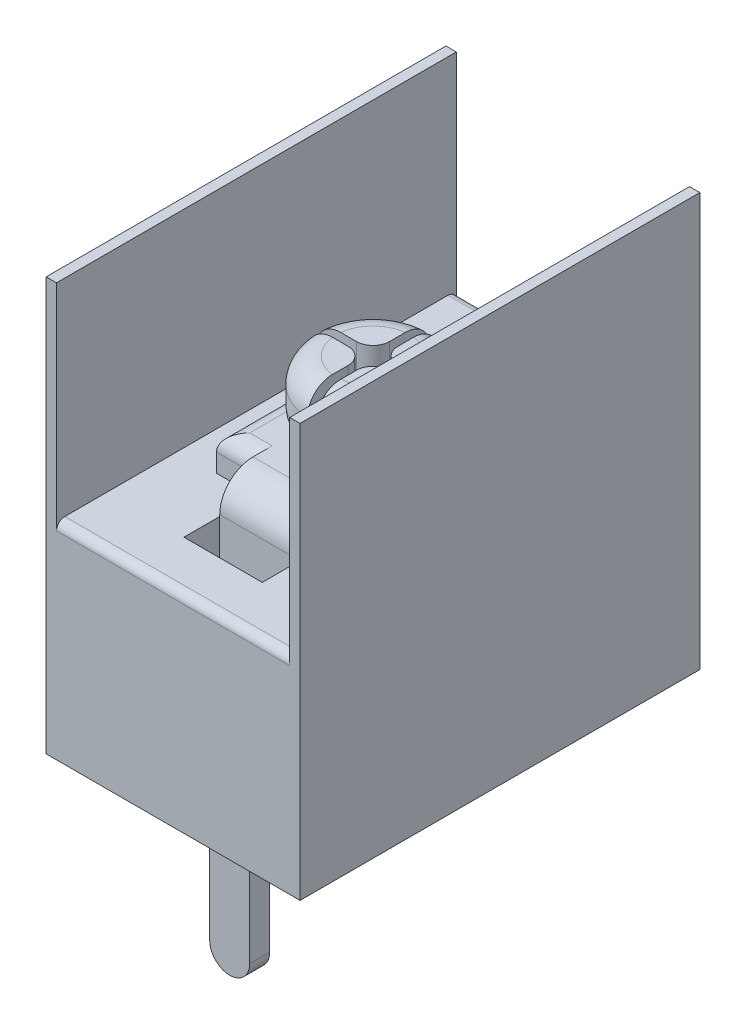
SolidWorks part; units mm, degrees
ref_plane "前视基准面" through (0, 0, 0) normal (0, 0, 1) x (1, 0, 0)
ref_plane "上视基准面" through (0, 0, 0) normal (0, 1, 0) x (1, 0, 0)
ref_plane "右视基准面" through (0, 0, 0) normal (1, 0, 0) x (0, 0, -1)
sketch "草图1" plane through (0, 0, 0) normal (0, 1, 0) x (1, 0, 0)
  line L1 (-3.81, -6) -> (3.81, -6)
  line L2 (-3.81, -6) -> (-3.81, 6)
  line L3 (-3.81, 6) -> (3.81, 6)
  line L4 (3.81, -6) -> (3.81, 6)
  line L5 (-3.81, -6) -> (3.81, 6) construction
  line L6 (-3.81, 6) -> (3.81, -6) construction
  point P1 (0, 0)
  dimension "D1" = 7.62
  dimension "D2" = 12
extrude "凸台-拉伸1" add sketch "草图1" along normal blind 12.4
sketch "草图2" plane through (0, 0, 0) normal (0, -1, 0) x (-1, 0, 0)
  line L0 (0, -6) -> (0, -4) construction
  line L1 (3.81, -6) -> (-3.81, -6) construction
  line L3 (0.6, -3.7) -> (-0.6, -3.7)
  line L4 (0.6, -3.7) -> (0.6, -4.3)
  line L5 (0.6, -4.3) -> (-0.6, -4.3)
  line L6 (-0.6, -3.7) -> (-0.6, -4.3)
  line L7 (0.6, -3.7) -> (-0.6, -4.3) construction
  line L8 (0.6, -4.3) -> (-0.6, -3.7) construction
  circle A0 centre (0, -4) radius 0.75 construction
  dimension "D4" = 1.5
  dimension "D1" = 2
  dimension "D2" = 1.2
  dimension "D3" = 0.6
extrude "凸台-拉伸2" add sketch "草图2" along normal blind 4.7 separate body
fillet "圆角1" radius 0.6 2 edges at (0.6, -4.7, 4) (-0.6, -4.7, 4)
sketch "草图3" plane through (0, 12.4, 0) normal (0, 1, 0) x (1, 0, 0)
  line L0 (3.81, 6) -> (-3.81, 6) construction
  line L1 (-3.5, -6) -> (3.5, -6)
  line L2 (-3.5, -6) -> (-3.5, 6)
  line L3 (-3.5, 6) -> (3.5, 6)
  line L4 (3.5, -6) -> (3.5, 6)
  line L5 (-3.5, -6) -> (3.5, 6) construction
  line L6 (-3.5, 6) -> (3.5, -6) construction
  point P0 (0, 0)
  dimension "D1" = 7
extrude "切除-拉伸1" cut sketch "草图3" against normal blind 6.2 contours L2 L3 L4 L1
sketch "草图4" plane through (0, 6.2, 0) normal (0, 1, 0) x (1, 0, 0)
  line L0 (1.175, 2.35) -> (2.35, 2.35)
  line L1 (-2.35, -2.35) -> (-1.175, -2.35)
  line L2 (-2.35, -2.35) -> (-2.35, 2.35)
  line L3 (-2.35, 2.35) -> (-1.175, 2.35)
  line L4 (2.35, -2.35) -> (2.35, 2.35)
  line L5 (-2.35, -2.35) -> (2.35, 2.35) construction
  line L6 (-2.35, 2.35) -> (2.35, -2.35) construction
  line L7 (1.175, 4.5) -> (-1.175, 4.5)
  line L8 (1.175, 4.5) -> (1.175, 2.35)
  line L9 (1.175, -4.5) -> (-1.175, -4.5)
  line L10 (-1.175, 4.5) -> (-1.175, 2.35)
  line L11 (1.175, 4.5) -> (-1.175, -4.5) construction
  line L12 (1.175, -4.5) -> (-1.175, 4.5) construction
  line L13 (-1.175, -2.35) -> (-1.175, -4.5)
  line L14 (1.175, -2.35) -> (2.35, -2.35)
  line L15 (1.175, -2.35) -> (1.175, -4.5)
  point P0 (0, 0)
  point P6 (0, 0)
  dimension "D1" = 4.7
  dimension "D2" = 4.7
  dimension "D3" = 9
  dimension "D4" = 2.35
extrude "切除-拉伸3" cut sketch "草图4" against normal blind 3.1 contours L3 L10 L7 L8 L0 L4 L14 L15 L9 L13 L1 L2
sketch "草图5" plane through (0, 3.1, 0) normal (0, 1, 0) x (1, 0, 0)
  line L0 (-2.35, 2.35) -> (-2.35, -2.35)
  line L1 (-2.35, -2.35) -> (-1.175, -2.35)
  line L2 (-1.175, -2.35) -> (-1.175, -3.425)
  line L3 (-1.175, -2.35) -> (-1.175, -4.5) construction
  line L4 (-1.175, -3.425) -> (1.175, -3.425)
  line L5 (1.175, -2.35) -> (1.175, -4.5) construction
  line L6 (1.175, -3.425) -> (1.175, -2.35)
  line L7 (1.175, -2.35) -> (2.35, -2.35)
  line L8 (2.35, -2.35) -> (2.35, 2.35)
  line L9 (2.35, 2.35) -> (1.175, 2.35)
  line L10 (1.175, 2.35) -> (1.175, 3.425)
  line L11 (1.175, 4.5) -> (1.175, 2.35) construction
  line L12 (1.175, 3.425) -> (-1.175, 3.425)
  line L13 (-1.175, 4.5) -> (-1.175, 2.35) construction
  line L14 (-1.175, 3.425) -> (-1.175, 2.35)
  line L15 (-1.175, 2.35) -> (-2.35, 2.35)
  circle A0 centre (0, 0) radius 1.5
  dimension "D1" = 3
extrude "凸台-拉伸4" add sketch "草图5" along normal blind 4.15 separate body
sketch "草图6" plane through (0, 3.1, 0) normal (0, 1, 0) x (1, 0, 0)
  circle A0 centre (0, 0) radius 1.5
extrude "凸台-拉伸5" add sketch "草图6" along normal blind 4.15 separate body
fillet "圆角2" radius 1 2 edges at (0, 7.25, -3.425) (0, 7.25, 3.425)
fillet "圆角3" radius 0.5 6 edges at (-2.35, 7.25, 0) (-1.7625, 7.25, 2.35) (1.7625, 7.25, 2.35) (1.7625, 7.25, -2.35) (-1.7625, 7.25, -2.35) (2.35, 7.25, 0)
sketch "草图7" plane through (0, 7.25, 0) normal (0, 1, 0) x (1, 0, 0)
  circle A0 centre (0, 0) radius 1.85
  point P0 (0, 0)
extrude "凸台-拉伸6" add sketch "草图7" along normal blind 2 separate body
fillet "圆角4" radius 0.75 2 edges at (0, 7.25, 1.85) (0, 9.25, 1.85)
sketch "草图8" plane through (0, 9.25, 0) normal (0, 1, 0) x (1, 0, 0)
  line L1 (-0.125, -2.5) -> (0.125, -2.5)
  line L2 (-0.125, -2.5) -> (-0.125, 2.5)
  line L3 (-0.125, 2.5) -> (0.125, 2.5)
  line L4 (0.125, -2.5) -> (0.125, 2.5)
  line L5 (-0.125, -2.5) -> (0.125, 2.5) construction
  line L6 (-0.125, 2.5) -> (0.125, -2.5) construction
  line L7 (-2.5, -0.125) -> (2.5, -0.125)
  line L8 (-2.5, -0.125) -> (-2.5, 0.125)
  line L9 (-2.5, 0.125) -> (2.5, 0.125)
  line L10 (2.5, -0.125) -> (2.5, 0.125)
  line L11 (-2.5, -0.125) -> (2.5, 0.125) construction
  line L12 (-2.5, 0.125) -> (2.5, -0.125) construction
  point P0 (0, 0)
  point P6 (0, 0)
  dimension "D1" = 0.25
  dimension "D2" = 5
  dimension "D3" = 5
  dimension "D4" = 0.25
extrude "切除-拉伸4" cut sketch "草图8" against normal blind 1 contours L4 L3 L2 L1 | L9 L10 L7 L8
fillet "圆角5" radius 0.5 4 edges at (0.125, 8.75, 0.125) (-0.125, 8.75, 0.125) (0.125, 8.75, -0.125) (-0.125, 8.75, -0.125)
fillet "圆角6" radius 0.25 2 edges at (0, 6.2, -6) (0, 6.2, 6)
combine bodies "组合1" operation type add bodies to combine 113 115
sketch "草图9" plane through (0, 0, 0) normal (0, -1, 0) x (1, 0, 0)
  line L0 (0, 4.3) -> (0, 3.7) construction
  circle A0 centre (0, 4) radius 0.75
  dimension "D1" = 1.5
extrude "切除-拉伸5" cut sketch "草图9" against normal blind 0.25
sketch "草图10" plane through (0, 0, 0) normal (0, 1, 0) x (1, 0, 0)
  line L1 (0.6, -3.7) -> (-0.6, -3.7)
  line L2 (0.6, -3.7) -> (0.6, -4.3)
  line L3 (0.6, -4.3) -> (-0.6, -4.3)
  line L4 (-0.6, -3.7) -> (-0.6, -4.3)
extrude "凸台-拉伸7" add sketch "草图10" along normal blind 0.25
equation "\"D1@切除-拉伸1\"=12.4/2"
equation "\"D4@草图4\"=4.7/2"
equation "\"D1@切除-拉伸3\"=12.4/4"
